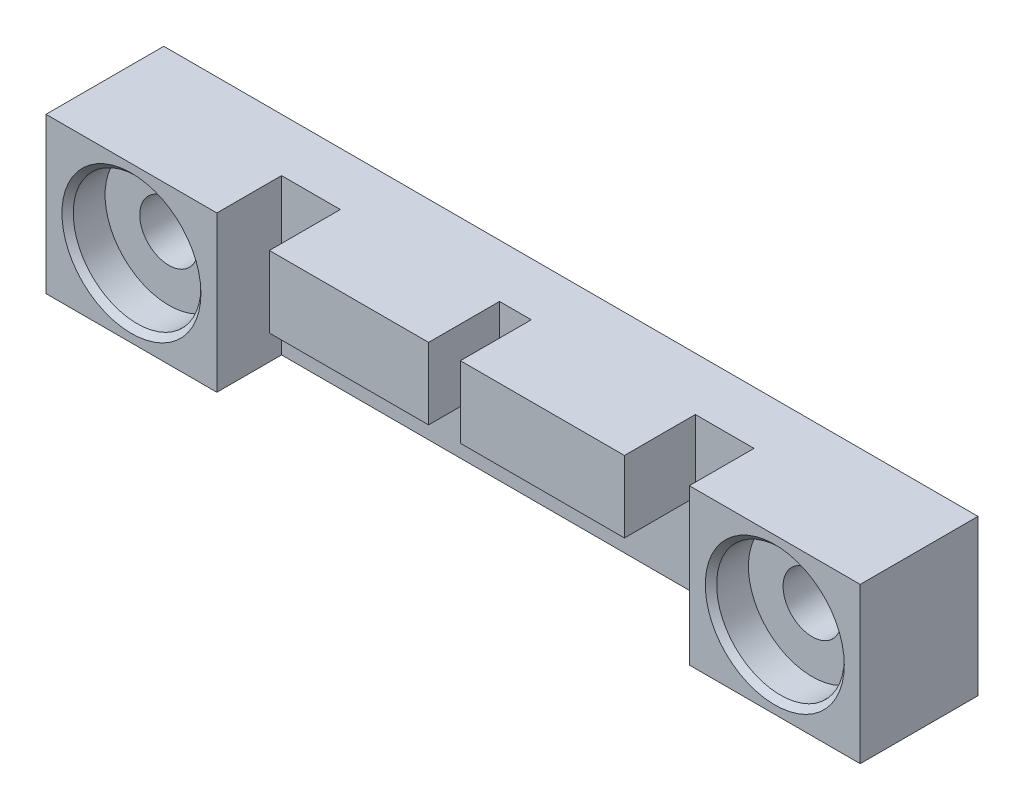
SolidWorks part; units mm, degrees
ref_plane "Front Plane" through (0, 0, 0) normal (0, 0, 1) x (1, 0, 0)
ref_plane "Top Plane" through (0, 0, 0) normal (0, 1, 0) x (1, 0, 0)
ref_plane "Right Plane" through (0, 0, 0) normal (1, 0, 0) x (0, 0, -1)
sketch "Sketch1" plane through (0, 0, 0) normal (0, 0, 1) x (1, 0, 0)
  line L1 (0, 0) -> (-91.1352, 0)
  line L2 (0, 0) -> (0, 17.3863)
  line L3 (0, 17.3863) -> (-91.1352, 17.3863)
  line L4 (-91.1352, 0) -> (-91.1352, 17.3863)
  dimension "D1" = 91.1352
  dimension "D2" = 17.3863
extrude "Boss-Extrude1" add sketch "Sketch1" along normal blind 13.1826
sketch "Sketch2" plane through (0, 0, 13.1826) normal (0, 0, 1) x (1, 0, 0)
  line L0 (0, 17.3863) -> (-91.1352, 17.3863) construction
  line L1 (-72.009, 17.3863) -> (-19.1262, 17.3863)
  line L2 (-72.009, 17.3863) -> (-72.009, 0)
  line L3 (-72.009, 0) -> (-19.1262, 0)
  line L4 (-19.1262, 17.3863) -> (-19.1262, 0)
  line L5 (-91.1352, 0) -> (0, 0) construction
  line L6 (0, 0) -> (0, 17.3863) construction
  dimension "D1" = 52.8828
  dimension "D2" = 19.1262
extrude "Cut-Extrude1" cut sketch "Sketch2" against normal blind 7.239
sketch "Sketch3" plane through (0, 0, 13.1826) normal (0, 0, 1) x (1, 0, 0)
  line L0 (-91.1352, 8.6931) -> (0, 8.6932) construction
  line L1 (-91.1352, 17.3863) -> (-91.1352, 0) construction
  line L2 (0, 0) -> (0, 17.3863) construction
  line L3 (0, 8.6932) -> (-9.5631, 17.3863) construction
  line L4 (0, 17.3863) -> (-19.1262, 17.3863) construction
  line L5 (-9.5631, 17.3863) -> (-9.5631, 0) construction
  line L6 (-19.1262, 0) -> (0, 0) construction
  line L7 (-9.5631, 0) -> (-81.5721, 0) construction
  line L8 (-91.1352, 0) -> (-72.009, 0) construction
  line L9 (-81.5721, 0) -> (-81.5721, 17.3863) construction
  line L10 (-72.009, 17.3863) -> (-91.1352, 17.3863) construction
  point P9 (-81.5721, 8.6931)
  point P19 (-9.5631, 8.6932)
hole_wizard "CBORE for 1/4 Binding Head Machine Screw1" positions "Sketch5" profile "Sketch6" counterbore size "1/4" standard "ANSI Inch" end condition through all
sketch "Sketch5" plane through (0, 0, 13.1826) normal (0, 0, 1) x (1, 0, 0)
  point P0 (-81.5721, 8.6931)
  point P3 (-9.5631, 8.6932)
sketch "Sketch6" plane through (-81.5721, 8.6931, 13.1826) normal (1, 0, 0) x (0, -1, 0)
  line L0 (0, 0) -> (0, 13.1826)
  line L1 (0, 13.1826) -> (3.2639, 13.1826)
  line L3 (3.2639, 13.1826) -> (3.2639, 4.191)
  line L4 (7.1437, 4.191) -> (3.2639, 4.191)
  line L5 (7.1437, 4.191) -> (7.1437, 0.635)
  line L6 (7.1437, 0.635) -> (7.7788, 0)
  line L7 (7.7788, 0) -> (0, 0)
  line L8 (-7.1437, 0.635) -> (-7.7788, 0) construction
  line L11 (0, -6.35) -> (0, 107.95) construction
  dimension "Thru Hole Dia." = 6.5278
  dimension "Thru Hole Depth" = 13.1826
  dimension "C'Bore Dia." = 14.2875
  dimension "C'Bore Depth" = 4.191
  dimension "Near C'Sink Dia." = 15.5575
  dimension "Near C'Sink Angle" = 90
sketch "Sketch7" plane through (0, 0, 5.9436) normal (0, 0, 1) x (1, 0, 0)
  line L0 (-19.1262, 17.3863) -> (-72.009, 17.3863) construction
  line L1 (-65.4304, 17.3863) -> (-47.6123, 17.3863)
  line L2 (-65.4304, 17.3863) -> (-65.4304, 9.3853)
  line L3 (-65.4304, 9.3853) -> (-47.6123, 9.3853)
  line L4 (-47.6123, 17.3863) -> (-47.6123, 9.3853)
  line L5 (-72.009, 17.3863) -> (-72.009, 0) construction
  line L6 (-44.0563, 17.3863) -> (-25.6921, 17.3863)
  line L7 (-44.0563, 17.3863) -> (-44.0563, 9.3853)
  line L8 (-44.0563, 9.3853) -> (-25.6921, 9.3853)
  line L9 (-25.6921, 17.3863) -> (-25.6921, 9.3853)
  line L10 (-19.1262, 0) -> (-19.1262, 17.3863) construction
  line L11 (-9.5631, 0) -> (-81.5721, 0) construction
  dimension "D1" = 6.5786
  dimension "D2" = 6.5659
  dimension "D3" = 3.556
  dimension "D4" = 18.3642
  dimension "D5" = 9.3853
  dimension "D6" = 9.3853
extrude "Boss-Extrude2" add sketch "Sketch7" along normal blind 7.9375
